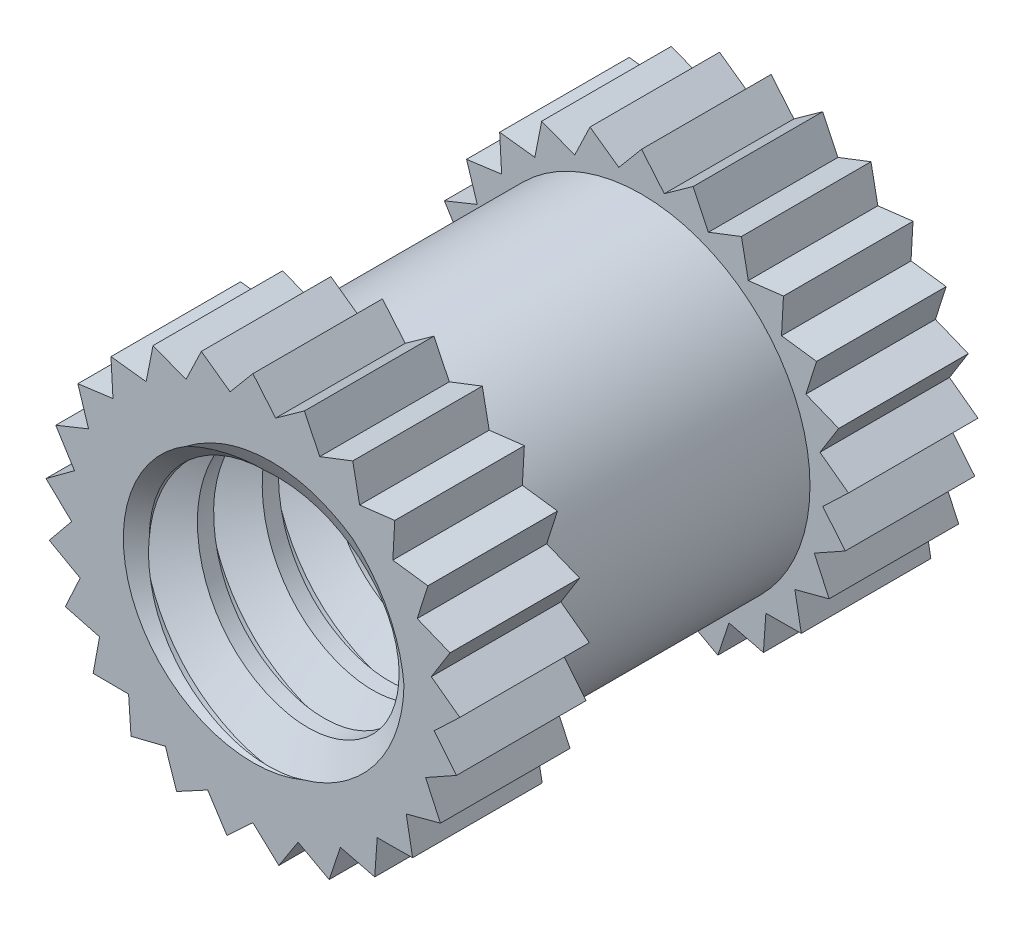
SolidWorks part; units mm, degrees
material "Brass"
ref_plane "Front Plane" through (0, 0, 0) normal (0, 0, 1) x (1, 0, 0)
ref_plane "Top Plane" through (0, 0, 0) normal (0, 1, 0) x (1, 0, 0)
ref_plane "Right Plane" through (0, 0, 0) normal (1, 0, 0) x (0, 0, -1)
sketch "Sketch1" plane through (0, 0, 0) normal (0, 0, 1) x (1, 0, 0)
  circle A1 centre (0, 0) radius 1.3
  dimension "D1" = 2.6
extrude "Boss-Extrude1" add sketch "Sketch1" along normal mid plane 4
hole_wizard "Tap Drill for M3x0.5 Tap1" positions "Sketch2" profile "Sketch3" hole size "M3x0.5" standard "ANSI Metric" end condition through all
sketch "Sketch2" plane through (0, 0, 2) normal (0, 0, 1) x (1, 0, 0)
  point P0 (0, 0)
sketch "Sketch3" plane through (0, 0, 2) normal (1, 0, 0) x (0, -1, 0)
  line L0 (0, 0) -> (0, 4)
  line L1 (0, 4) -> (1, 4)
  line L2 (0.9, 3.9) -> (0.9, 0.1)
  line L3 (0.9, 0.1) -> (1, 0)
  line L5 (1, 0) -> (0, 0)
  line L6 (-0.9, 0.1) -> (-1, 0) construction
  line L7 (1, 4) -> (0.9, 3.9)
  line L8 (-1, 4) -> (-0.9, 3.9) construction
  line L11 (0, -6.35) -> (0, 107.95) construction
  dimension "Thru Hole Dia." = 1.8
  dimension "Thru Hole Depth" = 4
  dimension "Near C'Sink Dia." = 2
  dimension "Near C'Sink Angle" = 90
  dimension "Far C'Sink Dia." = 2
  dimension "Far C'Sink Angle" = 90
thread "Thread1" pitch 0.5 method cut profile "Thread Profile1" start angle 0, offset 1, length 8, pitch 0.5, diameter 1.8
ref_plane "Plane1" through (-0.9, 0, 2.9) normal (0, -1, 0) x (-1, 0, 0)
sketch "Thread Profile1" plane through (-0.9, 0, 2.9) normal (0, -1, 0) x (-1, 0, 0)
  line L0 (0, 0) -> (0, 0.5) construction
  line L1 (0, 0) -> (0.2706, 0.1562)
  line L2 (0.2706, 0.1562) -> (0.2706, 0.2187)
  line L3 (0.2706, 0.2187) -> (0, 0.375)
  line L4 (0.2706, 0.1875) -> (0, 0.1875) construction
  line L11 (0, 0) -> (0, 0.375)
  point P2 (0, 0)
  dimension "Pitch" = 0.5
  dimension "Profile_Angle" = 60
  dimension "Profile_Land" = 0.0625
  dimension "Profile_Height" = 0.2706
sketch "Sketch6" plane through (0, 0, 2) normal (0, 0, 1) x (1, 0, 0)
  line L0 (0, 1.6) -> (0, 0) construction
  line L1 (0, 1.6) -> (-0.2767, 1.2702)
  line L2 (0, 1.6) -> (0.2767, 1.2702)
  circle A0 centre (0, 0) radius 1.6 construction
  circle A1 centre (0, 0) radius 1.3 construction
  arc A2 (0.2767, 1.2702) -> (-0.2767, 1.2702) centre (0, 0) ccw
  dimension "D2" = 80
extrude "Boss-Extrude2" add sketch "Sketch6" against normal blind 1
pattern_circular "CirPattern1" count 25 over 360 about axis through (0, 0, 2) along (0, 0, -1) of "Boss-Extrude2"
mirror "Mirror1" about plane through (0, 0, 0) normal (0, 0, 1) of "CirPattern1"
